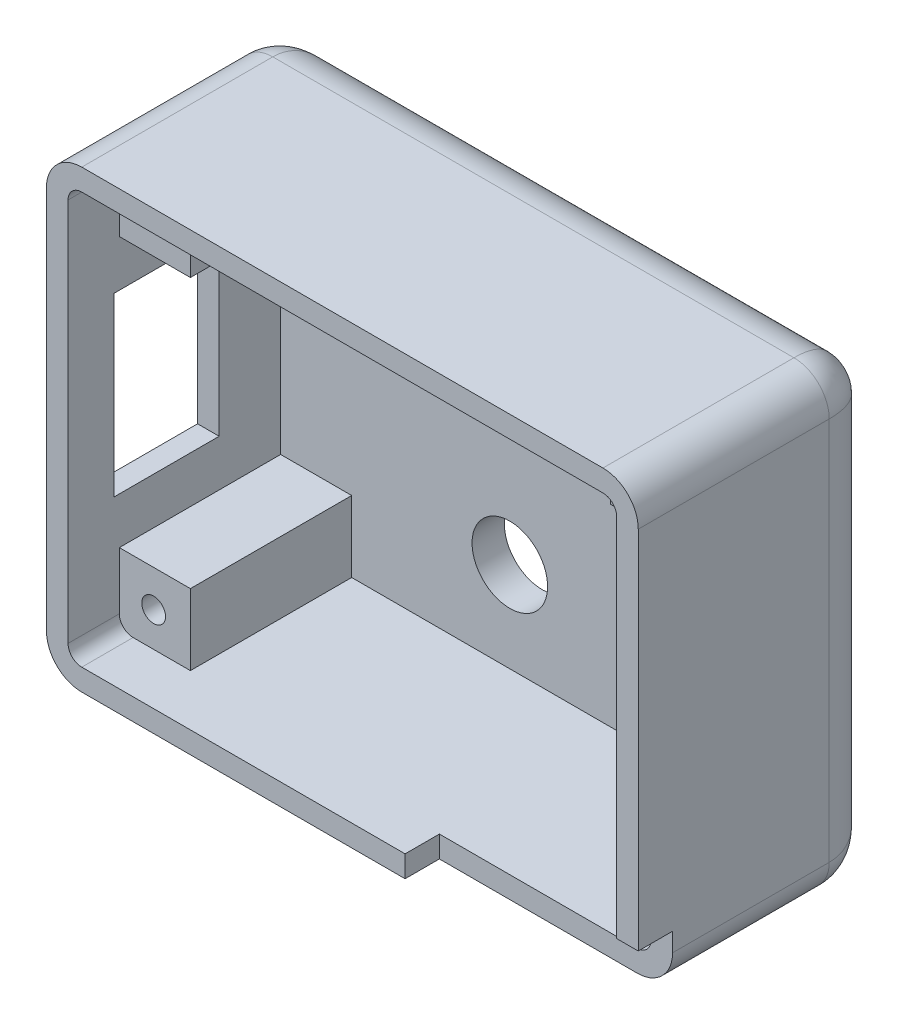
SolidWorks part; units mm, degrees
ref_plane "Front Plane" through (0, 0, 0) normal (0, 0, 1) x (1, 0, 0)
ref_plane "Top Plane" through (0, 0, 0) normal (0, 1, 0) x (1, 0, 0)
ref_plane "Right Plane" through (0, 0, 0) normal (1, 0, 0) x (0, 0, -1)
sketch "Sketch1" plane through (0, 0, 0) normal (0, 0, 1) x (1, 0, 0)
  line L0 (27.4, -17.78) -> (27.4, 17.78)
  line L1 (24.13, 21.05) -> (-24.13, 21.05)
  line L2 (-27.4, 17.78) -> (-27.4, -17.78)
  line L3 (-24.13, -21.05) -> (24.13, -21.05)
  line L4 (25.4, -17.78) -> (25.4, 17.78)
  line L5 (24.13, 19.05) -> (-24.13, 19.05)
  line L6 (-25.4, 17.78) -> (-25.4, -17.78)
  line L7 (-24.13, -19.05) -> (24.13, -19.05)
  line L8 (25.4, -17.78) -> (25.4, 17.78)
  line L9 (24.13, 19.05) -> (-24.13, 19.05)
  line L10 (-25.4, 17.78) -> (-25.4, -17.78)
  line L11 (-24.13, -19.05) -> (24.13, -19.05)
  arc A0 (27.4, 17.78) -> (24.13, 21.05) centre (24.13, 17.78) ccw
  arc A1 (-24.13, 21.05) -> (-27.4, 17.78) centre (-24.13, 17.78) ccw
  arc A2 (-27.4, -17.78) -> (-24.13, -21.05) centre (-24.13, -17.78) ccw
  arc A3 (24.13, -21.05) -> (27.4, -17.78) centre (24.13, -17.78) ccw
  arc A4 (25.4, 17.78) -> (24.13, 19.05) centre (24.13, 17.78) ccw
  arc A5 (-24.13, 19.05) -> (-25.4, 17.78) centre (-24.13, 17.78) ccw
  arc A6 (-25.4, -17.78) -> (-24.13, -19.05) centre (-24.13, -17.78) ccw
  arc A7 (24.13, -19.05) -> (25.4, -17.78) centre (24.13, -17.78) ccw
  arc A8 (25.4, 17.78) -> (24.13, 19.05) centre (24.13, 17.78) ccw
  arc A9 (-24.13, 19.05) -> (-25.4, 17.78) centre (-24.13, 17.78) ccw
  arc A10 (-25.4, -17.78) -> (-24.13, -19.05) centre (-24.13, -17.78) ccw
  arc A11 (24.13, -19.05) -> (25.4, -17.78) centre (24.13, -17.78) ccw
  dimension "D1" = 0
  dimension "D2" = 2
extrude "Boss-Extrude1" add sketch "Sketch1" against normal blind 16.51 and the other way blind 3.175
sketch "Sketch2" plane through (0, 0, -16.51) normal (0, 0, -1) x (-1, 0, 0)
  line L1 (-26.4422, 20.0922) -> (-20.0922, 20.0922)
  line L2 (-26.4422, 20.0922) -> (-26.4422, 13.7422)
  line L3 (-26.4422, 13.7422) -> (-20.0922, 13.7422)
  line L4 (-20.0922, 20.0922) -> (-20.0922, 13.7422)
  line L5 (26.4422, 20.0922) -> (18.8222, 20.0922)
  line L6 (26.4422, 20.0922) -> (26.4422, 12.4722)
  line L7 (26.4422, 12.4722) -> (18.8222, 12.4722)
  line L8 (18.8222, 20.0922) -> (18.8222, 12.4722)
  line L9 (26.4422, -20.0922) -> (18.8222, -20.0922)
  line L10 (26.4422, -20.0922) -> (26.4422, -12.4722)
  line L11 (26.4422, -12.4722) -> (18.8222, -12.4722)
  line L12 (18.8222, -20.0922) -> (18.8222, -12.4722)
  line L13 (-26.4422, -20.0922) -> (-22.225, -20.0922)
  line L14 (-26.4422, -20.0922) -> (-26.4422, -15.875)
  line L15 (-26.4422, -15.875) -> (-22.225, -15.875)
  line L16 (-22.225, -20.0922) -> (-22.225, -15.875)
  arc A0 (-24.13, 21.05) -> (-27.4, 17.78) centre (-24.13, 17.78) ccw construction
  arc A1 (27.4, 17.78) -> (24.13, 21.05) centre (24.13, 17.78) ccw construction
  arc A2 (24.13, -21.05) -> (27.4, -17.78) centre (24.13, -17.78) ccw construction
  circle A3 centre (22.225, -15.875) radius 1.1 construction
  circle A4 centre (22.225, 15.875) radius 1.1 construction
  circle A5 centre (-22.225, 15.875) radius 1.1 construction
  circle A6 centre (22.225, -15.875) radius 1.1
  circle A7 centre (22.225, 15.875) radius 1.1
  circle A8 centre (-22.225, 15.875) radius 1.1
  arc A9 (-27.4, -17.78) -> (-24.13, -21.05) centre (-24.13, -17.78) ccw construction
  dimension "D1" = 6.35
  dimension "D2" = 7.62
extrude "Boss-Extrude2" add sketch "Sketch2" against normal up to surface (14.9352 mm away)
sketch "Sketch3" plane through (0, 0, -16.51) normal (0, 0, -1) x (-1, 0, 0)
  line L4 (27.4, -17.78) -> (27.4, 17.78)
  line L5 (24.13, 21.05) -> (-24.13, 21.05)
  line L6 (-27.4, 17.78) -> (-27.4, -17.78)
  line L7 (-24.13, -21.05) -> (24.13, -21.05)
  line L8 (27.4, -17.78) -> (27.4, 17.78)
  line L9 (24.13, 21.05) -> (-24.13, 21.05)
  line L10 (-27.4, 17.78) -> (-27.4, -17.78)
  line L11 (-24.13, -21.05) -> (24.13, -21.05)
  arc A4 (27.4, 17.78) -> (24.13, 21.05) centre (24.13, 17.78) ccw
  arc A5 (-24.13, 21.05) -> (-27.4, 17.78) centre (-24.13, 17.78) ccw
  arc A6 (-27.4, -17.78) -> (-24.13, -21.05) centre (-24.13, -17.78) ccw
  arc A7 (24.13, -21.05) -> (27.4, -17.78) centre (24.13, -17.78) ccw
  arc A8 (27.4, 17.78) -> (24.13, 21.05) centre (24.13, 17.78) ccw
  arc A9 (-24.13, 21.05) -> (-27.4, 17.78) centre (-24.13, 17.78) ccw
  arc A10 (-27.4, -17.78) -> (-24.13, -21.05) centre (-24.13, -17.78) ccw
  arc A11 (24.13, -21.05) -> (27.4, -17.78) centre (24.13, -17.78) ccw
  dimension "D1" = 0
extrude "Boss-Extrude3" add sketch "Sketch3" along normal blind 3
fillet "Fillet1" radius 5 8 edges at (0, -21.05, -19.51) (26.4422, -20.0922, -19.51) (27.4, 0, -19.51) (26.4422, 20.0922, -19.51) (0, 21.05, -19.51) (-26.4422, 20.0922, -19.51) (-27.4, 0, -19.51) (-26.4422, -20.0922, -19.51)
sketch "Sketch4" plane through (0, 0, -19.51) normal (0, 0, -1) x (-1, 0, 0)
  circle A0 centre (2.4498, 10.878) radius 3.5
  circle A1 centre (4.1778, -10.7043) radius 3.5
  dimension "D1" = 7
extrude "Cut-Extrude1" cut sketch "Sketch4" against normal up to surface (3 mm away) up to face at (0.7788, -0.3555, -16.51)
sketch "Sketch5" plane through (-27.4, 0, 0) normal (-1, 0, 0) x (0, 0, 1)
  line L0 (3.175, 0) -> (-14.51, 0) construction
  line L1 (3.175, 17.78) -> (3.175, -17.78) construction
  line L2 (-14.51, 17.78) -> (-14.51, -17.78) construction
  line L4 (-1.0801, -8.1653) -> (-10.8166, -8.1653)
  line L5 (-1.0801, -8.1653) -> (-1.0801, 8.1653)
  line L6 (-1.0801, 8.1653) -> (-10.8166, 8.1653)
  line L7 (-10.8166, -8.1653) -> (-10.8166, 8.1653)
  line L8 (-1.0801, -8.1653) -> (-10.8166, 8.1653) construction
  line L9 (-1.0801, 8.1653) -> (-10.8166, -8.1653) construction
  point P6 (-5.9483, 0)
extrude "Cut-Extrude2" cut sketch "Sketch5" against normal blind 10
sketch "Sketch6" plane through (0, 0, 3.175) normal (0, 0, 1) x (1, 0, 0)
  line L0 (22.4, -16.05) -> (-22.4, -16.05) construction
  line L1 (27.4, -21.05) -> (5.81, -21.05)
  line L2 (27.4, -21.05) -> (27.4, -16.05)
  line L3 (27.4, -16.05) -> (5.81, -16.05)
  line L4 (5.81, -21.05) -> (5.81, -16.05)
  line L5 (7.08, -16.05) -> (27.4, -16.05) construction
  dimension "D1" = 21.59
extrude "Cut-Extrude3" cut sketch "Sketch6" against normal blind 3.175
